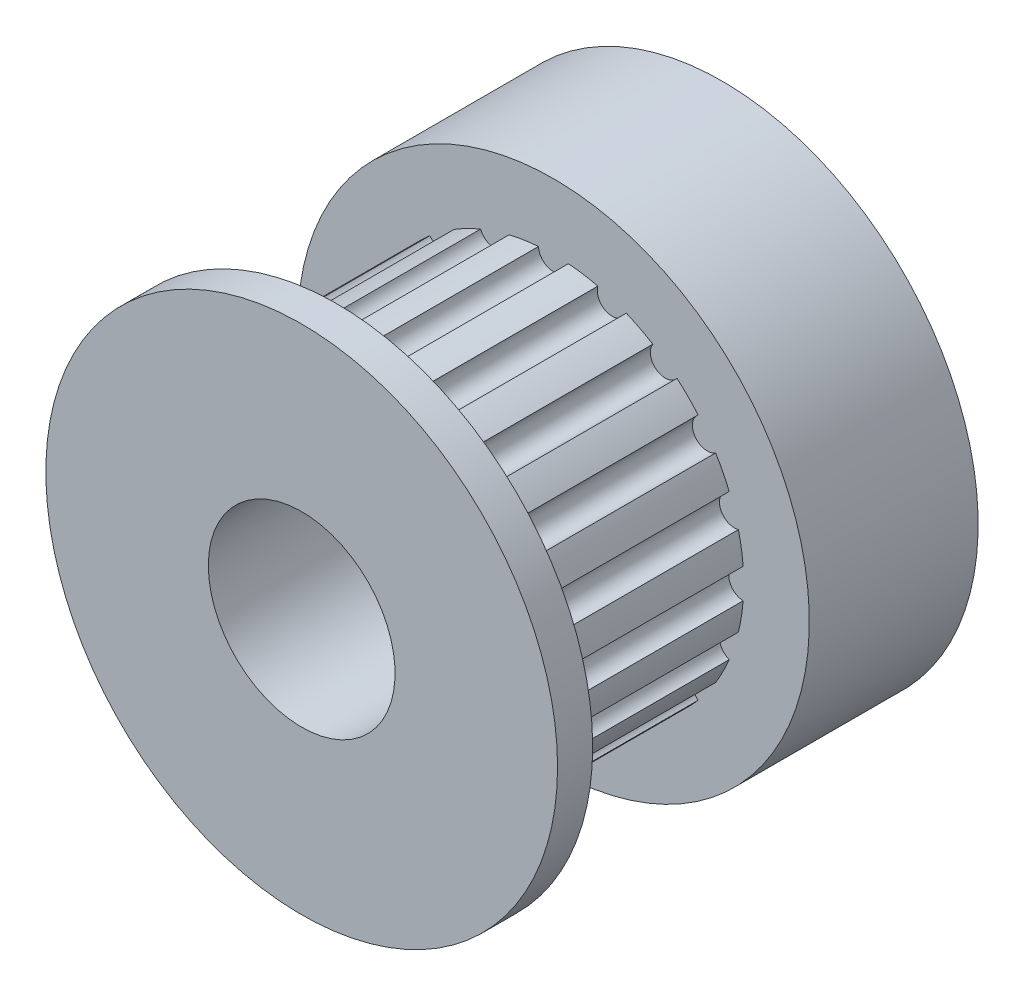
SolidWorks part; units mm, degrees
ref_plane "Plan de face" through (0, 0, 0) normal (0, 0, 1) x (1, 0, 0)
ref_plane "Plan de dessus" through (0, 0, 0) normal (0, 1, 0) x (1, 0, 0)
ref_plane "Plan de droite" through (0, 0, 0) normal (1, 0, 0) x (0, 0, -1)
sketch "Sketch1" plane through (0, 0, 0) normal (0, 0, 1) x (1, 0, 0)
  circle A0 centre (0, 0) radius 8.6995
  dimension "D1" = 17.399
extrude "Boss-Extrude1" add sketch "Sketch1" along normal blind 5.7404
sketch "Sketch2" plane through (0, 0, 5.7404) normal (0, 0, 1) x (1, 0, 0)
  circle A0 centre (0, 0) radius 6.4681
  dimension "D1" = 12.9361
extrude "Boss-Extrude2" add sketch "Sketch2" along normal blind 7.366
sketch "Sketch3" plane through (0, 0, 13.1064) normal (0, 0, 1) x (1, 0, 0)
  line L0 (0, -55) -> (0, 55) construction
  circle A0 centre (0, 6.4681) radius 0.508
  circle A1 centre (0, 0) radius 6.4681 construction
  dimension "D1" = 1.016
extrude "Cut-Extrude1" cut sketch "Sketch3" against normal up to surface (7.366 mm away) up to face at (6.4681, 0, 5.7404)
pattern_circular "CirPattern1" count 20 over 360 about axis through (0, 0, 13.1064) along (0, 0, 1) of "Cut-Extrude1"
sketch "Sketch4" plane through (0, 0, 13.1064) normal (0, 0, 1) x (1, 0, 0)
  circle A0 centre (0, 0) radius 8.6995
  dimension "D1" = 17.399
extrude "Boss-Extrude3" add sketch "Sketch4" along normal blind 1.1938
sketch "Sketch5" plane through (0, 0, 0) normal (0, 0, -1) x (-1, 0, 0)
  circle A0 centre (0, 0) radius 3.175
  dimension "D1" = 6.35
extrude "Cut-Extrude2" cut sketch "Sketch5" against normal through all
